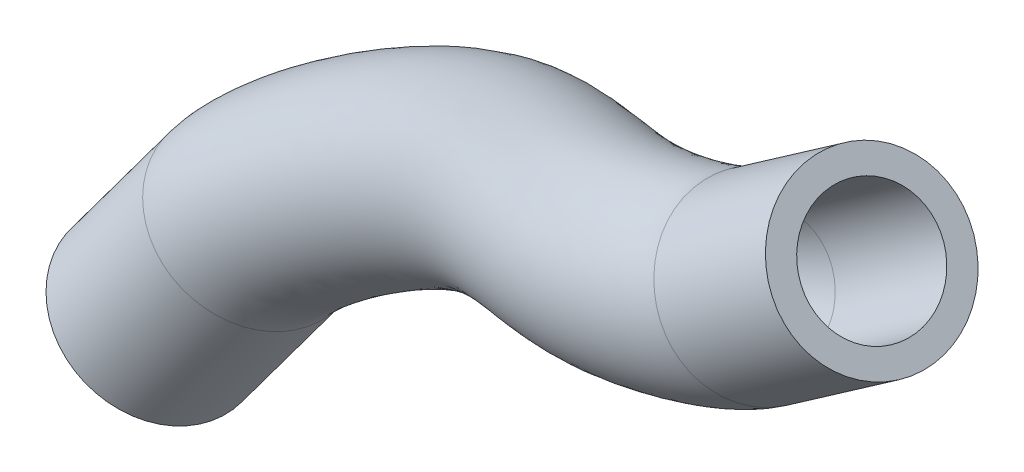
SolidWorks part; units mm, degrees
material "Silicon Rubber"
ref_plane "X-Y Datum" through (0, 0, 0) normal (0, 0, 1) x (1, 0, 0)
ref_plane "X-Z Datum" through (0, 0, 0) normal (0, 1, 0) x (1, 0, 0)
ref_plane "Y-Z Datum" through (0, 0, 0) normal (1, 0, 0) x (0, 0, -1)
sketch3d "3DSketch1"
  line L0 (0, 0, 0) -> (15.1451, 20.3909, 0)
  line L1 (126.7396, 83.3083, 32.0992) -> (147.0394, 98.3139, 34.9114)
  line L2 (0, 0, 0) -> (20.4458, 27.5277, 0) construction
  line L3 (147.0394, 98.3139, 34.9114) -> (129.2093, 85.1339, 32.4414) construction
  circle A0 centre (129.2093, 85.1339, 32.4414) radius 9.525 construction
  circle A1 centre (147.0394, 98.3139, 34.9114) radius 9.525 construction
  circle A4 centre (0, 0, 0) radius 9.6679 construction
  circle A5 centre (20.4458, 27.5277, 0) radius 7.366 construction
  circle A8 centre (129.2093, 85.1339, 32.4414) radius 9.525 construction
  circle A9 centre (147.0394, 98.3139, 34.9114) radius 9.525 construction
  circle A10 centre (0, 0, 0) radius 9.6679 construction
  circle A11 centre (20.4458, 27.5277, 0) radius 7.366 construction
  spline S0 degree 3 poles (15.1451, 20.3909, 0) (21.0657, 28.3622, 0) (47.9131, 46.0634, -5.1122) (102.4638, 73.7773, 31.9699) (121.7991, 79.6563, 31.4148) (126.7396, 83.3083, 32.0992) knots 0 0 0 0 0.424533 0.666181 1 1 1 1
  point P5 (0, 0, 0)
  point P8 (136.8217, 90.761, 33.4959)
  point P11 (154.6519, 103.941, 35.966)
  point P13 (136.8217, 90.761, 33.4959)
  point P15 (154.6519, 103.941, 35.966)
  point P16 (-5.7646, -7.7613, 0)
  point P19 (0, 0, 0)
  point P21 (24.8379, 33.441, 0)
  point P23 (-5.7646, -7.7613, 0)
  point P24 (0, 0, 0)
  point P26 (24.8379, 33.441, 0)
  point P27 (95.3098, 69.4473, 24.6913)
  dimension "D1" = 25.4
  dimension "D2" = 25.4
sweep "Sweep1" add path "3DSketch1" circular profile diameter 26.9875 parameters "D3"=26.9875
sweep "Cut-Sweep1" cut path "3DSketch1<2>" circular profile diameter 19.05 parameters "D3"=19.05
sketch3d "3DSketch1<2>" same geometry as "3DSketch1"
